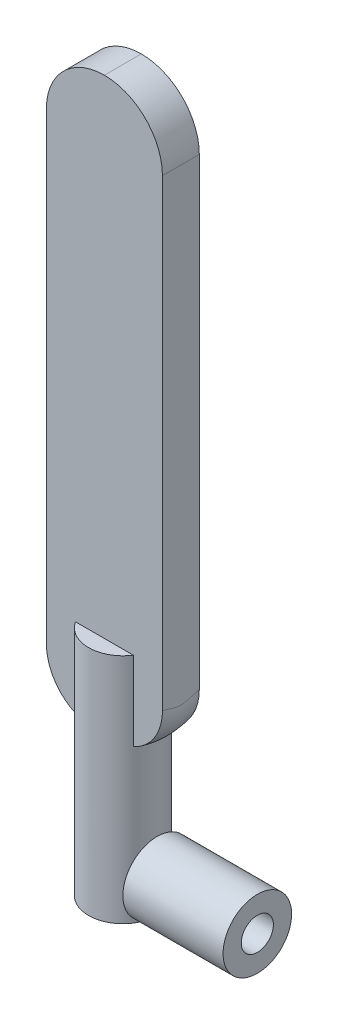
SolidWorks part; units mm, degrees
ref_plane "Спереди" through (0, 0, 0) normal (0, 0, 1) x (1, 0, 0)
ref_plane "Сверху" through (0, 0, 0) normal (0, 1, 0) x (1, 0, 0)
ref_plane "Справа" through (0, 0, 0) normal (1, 0, 0) x (0, 0, -1)
sketch "Эскиз1" plane through (0, 0, 0) normal (1, 0, 0) x (0, 0, -1)
  circle A0 centre (0, 0) radius 6.5
  dimension "D1" = 13
extrude "Бобышка-Вытянуть1" add sketch "Эскиз1" along normal blind 19
sketch "Эскиз2" plane through (19, 0, 0) normal (1, 0, 0) x (0, 0, -1)
  circle A0 centre (0, 0) radius 3.05
  dimension "D1" = 6.1
extrude "Вырез-Вытянуть1" cut sketch "Эскиз2" against normal blind 5
sketch "Эскиз3" plane through (0, 0, 0) normal (0, 1, 0) x (1, 0, 0)
  line L0 (0, 0) -> (-6.5, 0) construction
  line L1 (0, 6.5) -> (0, -6.5) construction
  circle A0 centre (-6.5, 0) radius 6.5
  dimension "D1" = 13
extrude "Бобышка-Вытянуть2" add sketch "Эскиз3" along normal blind 37.5 and the other way blind 6.5 separate body
sketch "Эскиз4" plane through (0, 37.5, 0) normal (0, 1, 0) x (1, 0, 0)
  line L0 (-17.5, -3.5) -> (4.5, 3.5) construction
  line L1 (-17.5, 3.5) -> (4.5, 3.5)
  line L2 (-17.5, 3.5) -> (-17.5, -3.5)
  line L3 (-17.5, -3.5) -> (4.5, -3.5)
  line L4 (4.5, 3.5) -> (4.5, -3.5)
  circle A0 centre (-6.5, 0) radius 6.5 construction
  point P7 (-6.5, 0)
  dimension "D1" = 22
  dimension "D2" = 7
extrude "Бобышка-Вытянуть3" add sketch "Эскиз4" along normal blind 92.5 and the other way blind 15
fillet "Скругление1" radius 11 2 edges at (-17.5, 130, 0) (4.5, 130, 0)
fillet "Скругление2" radius 9 2 edges at (-17.5, 22.5, 0) (4.5, 22.5, 0)
